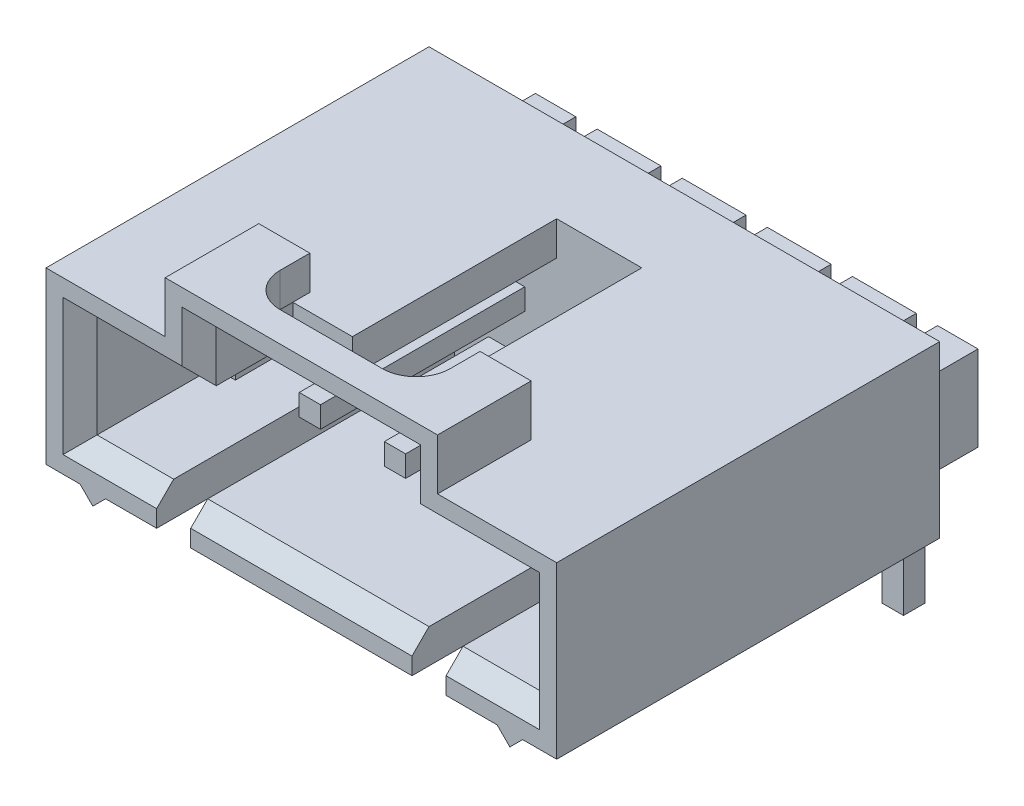
SolidWorks part; units mm, degrees
material "ABS"
ref_plane "Front Plane" through (0, 0, 0) normal (0, 0, 1) x (1, 0, 0)
ref_plane "Top Plane" through (0, 0, 0) normal (0, 1, 0) x (1, 0, 0)
ref_plane "Right Plane" through (0, 0, 0) normal (1, 0, 0) x (0, 0, -1)
ref_plane "Plane1" through (0, 0, -6.477) normal (0, 0, -1) x (-1, 0, 0)
sketch "Sketch1" plane through (0, 0, -6.477) normal (0, 0, -1) x (-1, 0, 0)
  line L0 (-6.604, 1.778) -> (-6.604, -1.778)
  line L1 (-6.604, -1.778) -> (6.604, -1.778)
  line L2 (6.604, -1.778) -> (6.604, 1.778)
  line L3 (6.604, 1.778) -> (-6.604, 1.778)
extrude "Boss-Extrude1" add sketch "Sketch1" against normal blind 0.762
sketch "Sketch2" plane through (0, 0, -6.477) normal (0, 0, -1) x (-1, 0, 0)
  line L0 (4.7625, -0.3832) -> (4.7625, 0.2791)
  line L1 (4.7625, 0.2791) -> (5.3975, 0.2791)
  line L2 (5.3975, 0.2791) -> (5.3975, -0.3832)
  line L3 (5.3975, -0.3832) -> (4.7625, -0.3832)
extrude "Boss-Extrude2" add sketch "Sketch2" along normal blind 1.016
sketch "Sketch3" plane through (0, 0, -6.477) normal (0, 0, -1) x (-1, 0, 0)
  line L0 (2.2225, -0.3832) -> (2.2225, 0.2791)
  line L1 (2.2225, 0.2791) -> (2.8575, 0.2791)
  line L2 (2.8575, 0.2791) -> (2.8575, -0.3832)
  line L3 (2.8575, -0.3832) -> (2.2225, -0.3832)
extrude "Boss-Extrude3" add sketch "Sketch3" along normal blind 1.016
sketch "Sketch4" plane through (0, 0, -6.477) normal (0, 0, -1) x (-1, 0, 0)
  line L0 (-0.3175, -0.3832) -> (-0.3175, 0.2791)
  line L1 (-0.3175, 0.2791) -> (0.3175, 0.2791)
  line L2 (0.3175, 0.2791) -> (0.3175, -0.3832)
  line L3 (0.3175, -0.3832) -> (-0.3175, -0.3832)
extrude "Boss-Extrude4" add sketch "Sketch4" along normal blind 1.016
sketch "Sketch5" plane through (0, 0, -6.477) normal (0, 0, -1) x (-1, 0, 0)
  line L0 (-2.8575, -0.3832) -> (-2.8575, 0.2791)
  line L1 (-2.8575, 0.2791) -> (-2.2225, 0.2791)
  line L2 (-2.2225, 0.2791) -> (-2.2225, -0.3832)
  line L3 (-2.2225, -0.3832) -> (-2.8575, -0.3832)
extrude "Boss-Extrude5" add sketch "Sketch5" along normal blind 1.016
sketch "Sketch6" plane through (0, 0, -6.477) normal (0, 0, -1) x (-1, 0, 0)
  line L0 (-5.3975, -0.3832) -> (-5.3975, 0.2791)
  line L1 (-5.3975, 0.2791) -> (-4.7625, 0.2791)
  line L2 (-4.7625, 0.2791) -> (-4.7625, -0.3832)
  line L3 (-4.7625, -0.3832) -> (-5.3975, -0.3832)
extrude "Boss-Extrude6" add sketch "Sketch6" along normal blind 1.016
sketch "Sketch7" plane through (0, -0.3832, 0) normal (0, -1, 0) x (1, 0, 0)
  line L0 (5.3975, -7.493) -> (4.7625, -7.493)
  line L1 (4.7625, -7.493) -> (4.7625, -6.858)
  line L2 (4.7625, -6.858) -> (5.3975, -6.858)
  line L3 (5.3975, -6.858) -> (5.3975, -7.493)
extrude "Boss-Extrude7" add sketch "Sketch7" along normal blind 5.8398
sketch "Sketch8" plane through (0, -0.3832, 0) normal (0, -1, 0) x (1, 0, 0)
  line L0 (2.8575, -7.493) -> (2.2225, -7.493)
  line L1 (2.2225, -7.493) -> (2.2225, -6.858)
  line L2 (2.2225, -6.858) -> (2.8575, -6.858)
  line L3 (2.8575, -6.858) -> (2.8575, -7.493)
extrude "Boss-Extrude8" add sketch "Sketch8" along normal blind 5.8398
sketch "Sketch9" plane through (0, -0.3832, 0) normal (0, -1, 0) x (1, 0, 0)
  line L0 (0.3175, -7.493) -> (-0.3175, -7.493)
  line L1 (-0.3175, -7.493) -> (-0.3175, -6.858)
  line L2 (-0.3175, -6.858) -> (0.3175, -6.858)
  line L3 (0.3175, -6.858) -> (0.3175, -7.493)
extrude "Boss-Extrude9" add sketch "Sketch9" along normal blind 5.8398
sketch "Sketch10" plane through (0, -0.3832, 0) normal (0, -1, 0) x (1, 0, 0)
  line L0 (-2.2225, -7.493) -> (-2.8575, -7.493)
  line L1 (-2.8575, -7.493) -> (-2.8575, -6.858)
  line L2 (-2.8575, -6.858) -> (-2.2225, -6.858)
  line L3 (-2.2225, -6.858) -> (-2.2225, -7.493)
extrude "Boss-Extrude10" add sketch "Sketch10" along normal blind 5.8398
sketch "Sketch11" plane through (0, -0.3832, 0) normal (0, -1, 0) x (1, 0, 0)
  line L0 (-4.7625, -7.493) -> (-5.3975, -7.493)
  line L1 (-5.3975, -7.493) -> (-5.3975, -6.858)
  line L2 (-5.3975, -6.858) -> (-4.7625, -6.858)
  line L3 (-4.7625, -6.858) -> (-4.7625, -7.493)
extrude "Boss-Extrude11" add sketch "Sketch11" along normal blind 5.8398
ref_plane "Plane2" through (0, 0, -5.715) normal (0, 0, -1) x (-1, 0, 0)
sketch "Sketch12" plane through (0, 0, -5.715) normal (0, 0, -1) x (-1, 0, 0)
  line L0 (7.62, 2.54) -> (-7.62, 2.54)
  line L1 (-7.62, 2.54) -> (-7.62, -2.54)
  line L2 (-7.62, -2.54) -> (-6.604, -2.54)
  line L3 (-6.604, -2.54) -> (-5.842, -3.302)
  line L4 (-5.842, -3.302) -> (-5.842, -2.54)
  line L5 (-5.842, -2.54) -> (5.842, -2.54)
  line L6 (5.842, -2.54) -> (5.842, -3.302)
  line L7 (5.842, -3.302) -> (6.604, -2.54)
  line L8 (6.604, -2.54) -> (7.62, -2.54)
  line L9 (7.62, -2.54) -> (7.62, 2.54)
extrude "Boss-Extrude12" add sketch "Sketch12" against normal blind 11.43
ref_plane "Plane3" through (0, 0, -3.175) normal (0, 0, -1) x (-1, 0, 0)
sketch "Sketch13" plane through (0, 0, -3.175) normal (0, 0, -1) x (-1, 0, 0)
  line L0 (-4.318, -2.54) -> (4.318, -2.54)
  line L1 (4.318, -2.54) -> (4.318, -1.524)
  line L2 (4.318, -1.524) -> (6.604, -1.524)
  line L3 (6.604, -1.524) -> (6.604, 1.524)
  line L4 (6.604, 1.524) -> (1.27, 1.524)
  line L5 (1.27, 1.524) -> (1.27, 2.54)
  line L6 (1.27, 2.54) -> (-1.27, 2.54)
  line L7 (-1.27, 2.54) -> (-1.27, 1.524)
  line L8 (-1.27, 1.524) -> (-6.604, 1.524)
  line L9 (-6.604, 1.524) -> (-6.604, -1.524)
  line L10 (-6.604, -1.524) -> (-4.318, -1.524)
  line L11 (-4.318, -1.524) -> (-4.318, -2.54)
extrude "Cut-Extrude1" cut sketch "Sketch13" against normal up to next
sketch "Sketch14" plane through (0, 0, 5.715) normal (0, 0, 1) x (1, 0, 0)
  line L0 (3.048, 1.524) -> (3.048, 2.54)
  line L1 (3.048, 2.54) -> (1.27, 2.54)
  line L2 (1.27, 2.54) -> (1.27, 1.524)
  line L3 (1.27, 1.524) -> (3.048, 1.524)
extrude "Cut-Extrude2" cut sketch "Sketch14" against normal blind 2.794
sketch "Sketch15" plane through (0, 0, 5.715) normal (0, 0, 1) x (1, 0, 0)
  line L0 (-1.27, 2.54) -> (-3.048, 2.54)
  line L1 (-3.048, 2.54) -> (-3.048, 1.524)
  line L2 (-3.048, 1.524) -> (-1.27, 1.524)
  line L3 (-1.27, 1.524) -> (-1.27, 2.54)
extrude "Cut-Extrude3" cut sketch "Sketch15" against normal blind 2.794
ref_plane "Plane4" through (0, 0, 5.715) normal (0, 0, 1) x (1, 0, 0)
sketch "Sketch16" plane through (0, 0, 5.715) normal (0, 0, 1) x (1, 0, 0)
  line L0 (-3.048, 3.048) -> (3.048, 3.048)
  line L1 (3.048, 3.048) -> (3.048, 2.54)
  line L2 (3.048, 2.54) -> (4.064, 2.54)
  line L3 (4.064, 2.54) -> (4.064, 4.064)
  line L4 (4.064, 4.064) -> (-4.064, 4.064)
  line L5 (-4.064, 4.064) -> (-4.064, 2.54)
  line L6 (-4.064, 2.54) -> (-3.048, 2.54)
  line L7 (-3.048, 2.54) -> (-3.048, 3.048)
extrude "Boss-Extrude13" add sketch "Sketch16" against normal blind 2.794
sketch "Sketch17" plane through (0, 0, -3.175) normal (0, 0, 1) x (1, 0, 0)
  line L0 (3.302, -1.524) -> (3.302, -2.54)
  line L1 (3.302, -2.54) -> (-3.302, -2.54)
  line L2 (-3.302, -2.54) -> (-3.302, -1.524)
  line L3 (-3.302, -1.524) -> (3.302, -1.524)
extrude "Boss-Extrude14" add sketch "Sketch17" along normal blind 8.89
sketch "Sketch18" plane through (0, 0, 2.921) normal (0, 0, -1) x (-1, 0, 0)
  line L0 (2.54, 4.064) -> (-2.54, 4.064)
  line L1 (-2.54, 4.064) -> (-2.54, 3.048)
  line L2 (-2.54, 3.048) -> (2.54, 3.048)
  line L3 (2.54, 3.048) -> (2.54, 4.064)
extrude "Cut-Extrude4" cut sketch "Sketch18" against normal blind 1.905
chamfer "Chamfer1" distance 0.508 angle 45 1 edges at (2.159, 1.524, 2.921)
chamfer "Chamfer2" distance 0.508 angle 45 1 edges at (-2.159, 1.524, 2.921)
chamfer "Chamfer3" distance 0.508 angle 45 1 edges at (0, -1.524, 5.715)
draft "Draft1" type of draft neutral plane draft angle 45 faces to draft 2 face at (5.842, -2.921, 0) face at (-5.842, -2.921, 0) neutral plane through (5.842, -2.54, 5.715) neutral plane normal (0, -1, 0) parameters "D1"=45
chamfer "Chamfer4" distance 0.508 angle 45 9 edges at (5.461, -1.524, 5.715) (6.604, 0, 5.715) (4.826, 1.524, 5.715) (3.048, 2.286, 5.715) (0, 3.048, 5.715) (-3.048, 2.286, 5.715) (-4.826, 1.524, 5.715) (-5.461, -1.524, 5.715) (-6.604, 0, 5.715)
sketch "Sketch19" plane through (0, 0, -3.175) normal (0, 0, 1) x (1, 0, 0)
  line L0 (5.3975, -0.3302) -> (4.7625, -0.3302)
  line L1 (4.7625, -0.3302) -> (4.7625, 0.3048)
  line L2 (4.7625, 0.3048) -> (5.3975, 0.3048)
  line L3 (5.3975, 0.3048) -> (5.3975, -0.3302)
extrude "Boss-Extrude15" add sketch "Sketch19" along normal blind 6.096
sketch "Sketch20" plane through (0, 0, -3.175) normal (0, 0, 1) x (1, 0, 0)
  line L0 (2.8575, -0.3302) -> (2.2225, -0.3302)
  line L1 (2.2225, -0.3302) -> (2.2225, 0.3048)
  line L2 (2.2225, 0.3048) -> (2.8575, 0.3048)
  line L3 (2.8575, 0.3048) -> (2.8575, -0.3302)
extrude "Boss-Extrude16" add sketch "Sketch20" along normal blind 6.096
sketch "Sketch21" plane through (0, 0, -3.175) normal (0, 0, 1) x (1, 0, 0)
  line L0 (0.3175, -0.3302) -> (-0.3175, -0.3302)
  line L1 (-0.3175, -0.3302) -> (-0.3175, 0.3048)
  line L2 (-0.3175, 0.3048) -> (0.3175, 0.3048)
  line L3 (0.3175, 0.3048) -> (0.3175, -0.3302)
extrude "Boss-Extrude17" add sketch "Sketch21" along normal blind 6.096
sketch "Sketch22" plane through (0, 0, -3.175) normal (0, 0, 1) x (1, 0, 0)
  line L0 (-2.2225, -0.3302) -> (-2.8575, -0.3302)
  line L1 (-2.8575, -0.3302) -> (-2.8575, 0.3048)
  line L2 (-2.8575, 0.3048) -> (-2.2225, 0.3048)
  line L3 (-2.2225, 0.3048) -> (-2.2225, -0.3302)
extrude "Boss-Extrude18" add sketch "Sketch22" along normal blind 6.096
ref_plane "Plane5" through (0, 0, 2.921) normal (0, 0, 1) x (1, 0, 0)
sketch "Sketch23" plane through (0, 0, 2.921) normal (0, 0, 1) x (1, 0, 0)
  line L0 (-5.3975, -0.3302) -> (-4.7625, -0.3302)
  line L1 (-4.7625, -0.3302) -> (-4.7625, 0.3048)
  line L2 (-4.7625, 0.3048) -> (-5.3975, 0.3048)
  line L3 (-5.3975, 0.3048) -> (-5.3975, -0.3302)
extrude "Boss-Extrude19" add sketch "Sketch23" against normal up to surface (6.096 mm away) up to face at (0, -0.0127, -3.175)
fillet "Fillet1" radius 0.635 1 edges at (-5.08, -0.3832, -6.858) tangent propagation no
fillet "Fillet2" radius 0.635 1 edges at (-2.54, -0.3832, -6.858) tangent propagation no
fillet "Fillet3" radius 0.635 1 edges at (0, -0.3832, -6.858) tangent propagation no
fillet "Fillet4" radius 0.635 1 edges at (2.54, -0.3832, -6.858) tangent propagation no
fillet "Fillet5" radius 0.635 1 edges at (5.08, -0.3832, -6.858) tangent propagation no
fillet "Fillet6" radius 1.27 1 edges at (-5.08, 0.2791, -7.493) tangent propagation no
fillet "Fillet7" radius 1.27 1 edges at (-2.54, 0.2791, -7.493) tangent propagation no
fillet "Fillet8" radius 1.27 1 edges at (0, 0.2791, -7.493) tangent propagation no
fillet "Fillet9" radius 1.27 1 edges at (2.54, 0.2791, -7.493) tangent propagation no
fillet "Fillet10" radius 1.27 1 edges at (5.08, 0.2791, -7.493) tangent propagation no
ref_plane "Plane6" through (0, 0, -7.874) normal (0, 0, -1) x (-1, 0, 0)
sketch "Sketch24" plane through (0, 0, -7.874) normal (0, 0, -1) x (-1, 0, 0)
  line L0 (0.3175, -1.778) -> (2.2225, -1.778)
  line L1 (2.2225, -1.778) -> (2.2225, 0.762)
  line L2 (2.2225, 0.762) -> (0.3175, 0.762)
  line L3 (0.3175, 0.762) -> (0.3175, -1.778)
extrude "Boss-Extrude20" add sketch "Sketch24" against normal up to surface (1.397 mm away) up to face at (0, 0, -6.477)
sketch "Sketch25" plane through (0, 0, -7.874) normal (0, 0, -1) x (-1, 0, 0)
  line L0 (-2.2225, -1.778) -> (-0.3175, -1.778)
  line L1 (-0.3175, -1.778) -> (-0.3175, 0.762)
  line L2 (-0.3175, 0.762) -> (-2.2225, 0.762)
  line L3 (-2.2225, 0.762) -> (-2.2225, -1.778)
extrude "Boss-Extrude21" add sketch "Sketch25" against normal up to surface (1.397 mm away) up to face at (-0.9525, -0.153, -6.477)
sketch "Sketch26" plane through (0, 0, -7.874) normal (0, 0, -1) x (-1, 0, 0)
  line L0 (2.8575, -1.778) -> (4.7625, -1.778)
  line L1 (4.7625, -1.778) -> (4.7625, 0.762)
  line L2 (4.7625, 0.762) -> (2.8575, 0.762)
  line L3 (2.8575, 0.762) -> (2.8575, -1.778)
extrude "Boss-Extrude22" add sketch "Sketch26" against normal up to surface (1.397 mm away) up to face at (0, -0.0183, -6.477)
sketch "Sketch27" plane through (0, 0, -7.874) normal (0, 0, -1) x (-1, 0, 0)
  line L0 (6.604, -1.778) -> (6.604, 0.762)
  line L1 (6.604, 0.762) -> (5.3975, 0.762)
  line L2 (5.3975, 0.762) -> (5.3975, -1.778)
  line L3 (5.3975, -1.778) -> (6.604, -1.778)
extrude "Boss-Extrude23" add sketch "Sketch27" against normal up to surface (1.397 mm away) up to face at (-1.0583, 0.0715, -6.477)
sketch "Sketch28" plane through (0, 0, -7.874) normal (0, 0, -1) x (-1, 0, 0)
  line L0 (-4.7625, -1.778) -> (-2.8575, -1.778)
  line L1 (-2.8575, -1.778) -> (-2.8575, 0.762)
  line L2 (-2.8575, 0.762) -> (-4.7625, 0.762)
  line L3 (-4.7625, 0.762) -> (-4.7625, -1.778)
extrude "Boss-Extrude24" add sketch "Sketch28" against normal up to surface (1.397 mm away) up to face at (-0.7216, 0.3438, -6.477)
sketch "Sketch29" plane through (0, 0, -7.874) normal (0, 0, -1) x (-1, 0, 0)
  line L0 (-6.604, -1.778) -> (-5.3975, -1.778)
  line L1 (-5.3975, -1.778) -> (-5.3975, 0.762)
  line L2 (-5.3975, 0.762) -> (-6.604, 0.762)
  line L3 (-6.604, 0.762) -> (-6.604, -1.778)
extrude "Boss-Extrude25" add sketch "Sketch29" against normal up to surface (1.397 mm away) up to face at (0.3663, 0.371, -6.477)
fillet "Fillet11" radius 1.016 1 edges at (2.54, 3.556, 4.826) tangent propagation no
fillet "Fillet12" radius 1.016 1 edges at (-2.54, 3.556, 4.826) tangent propagation no
ref_plane "Plane7" through (0, 0, -7.1755) normal (0, 0, -1) x (-1, 0, 0)
sketch "Sketch30" plane through (0, 0, -7.1755) normal (0, 0, -1) x (-1, 0, 0)
  line L0 (-4.7625, -6.223) -> (-5.3975, -6.223) construction
  line L1 (-4.7625, -6.223) -> (-5.3975, -6.223) construction
  line L2 (-5.08, -1006.223) -> (-5.08, 48993.777) construction
  point P5 (-5.08, -6.223)
